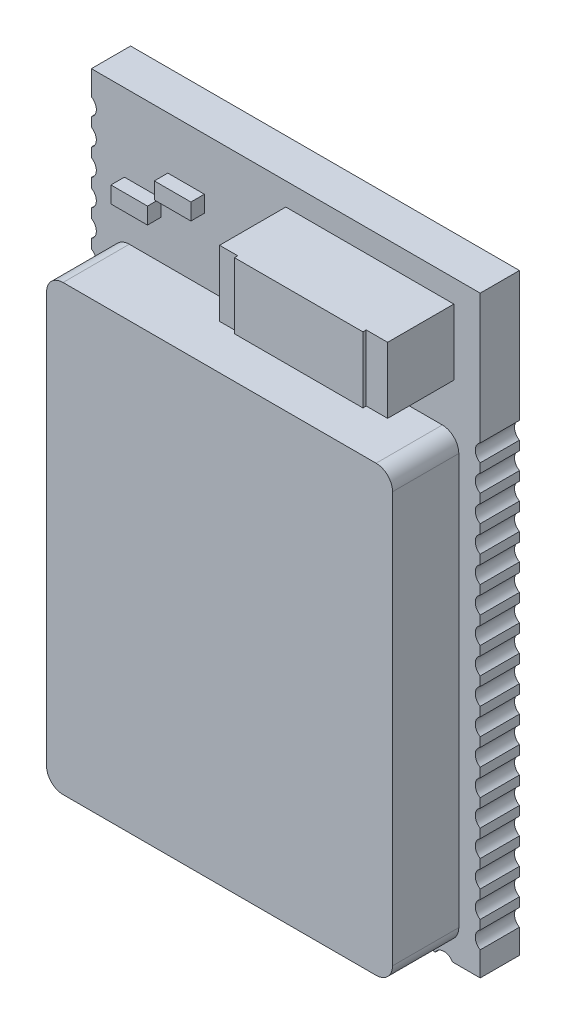
SolidWorks part; units mm, degrees
ref_plane "Front Plane" through (0, 0, 0) normal (0, 0, 1) x (1, 0, 0)
ref_plane "Top Plane" through (0, 0, 0) normal (0, 1, 0) x (1, 0, 0)
ref_plane "Right Plane" through (0, 0, 0) normal (1, 0, 0) x (0, 0, -1)
sketch "Sketch1" plane through (0, 0, 0) normal (0, 0, 1) x (1, 0, 0)
  line L1 (0, 0) -> (11.8, 0)
  line L2 (0, 0) -> (0, 18)
  line L3 (0, 18) -> (11.8, 18)
  line L4 (11.8, 0) -> (11.8, 18)
  dimension "D1" = 11.8
  dimension "D2" = 18
extrude "Boss-Extrude1" add sketch "Sketch1" along normal blind 1.19
sketch "Sketch2" plane through (0, 0, 0) normal (0, 0, 1) x (1, 0, 0)
  line L1 (0.65, 0.5) -> (11.15, 0.5)
  line L2 (0.65, 0.5) -> (0.65, 13.96)
  line L3 (0.65, 13.96) -> (11.15, 13.96)
  line L4 (11.15, 0.5) -> (11.15, 13.96)
extrude "Boss-Extrude2" add sketch "Sketch2" along normal blind 3.2
fillet "Fillet11" radius 0.5 1 edges at (0.65, 13.96, 2.195) type face fillet first side face at (0.65, 7.23, 2.195) second side face at (5.9, 13.96, 2.195)
fillet "Fillet12" radius 0.5 1 edges at (0.65, 0.5, 2.195) type face fillet first side face at (0.65, 6.98, 2.195) second side face at (5.9, 0.5, 2.195)
fillet "Fillet13" radius 0.5 1 edges at (11.15, 0.5, 2.195) type face fillet first side face at (6.15, 0.5, 2.195) second side face at (11.15, 7.23, 2.195)
fillet "Fillet14" radius 0.5 1 edges at (11.15, 13.96, 2.195) type face fillet first side face at (11.15, 7.48, 2.195) second side face at (6.15, 13.96, 2.195)
sketch "Sketch9" plane through (0, 0, 0) normal (0, 0, 1) x (1, 0, 0)
  circle A0 centre (1.1, -0.15) radius 0.3
  circle A1 centre (1.9, -0.15) radius 0.3
  circle A2 centre (2.7, -0.15) radius 0.3
  circle A3 centre (3.5, -0.15) radius 0.3
  circle A4 centre (4.3, -0.15) radius 0.3
  circle A5 centre (5.1, -0.15) radius 0.3
  circle A6 centre (5.9, -0.15) radius 0.3
  circle A7 centre (6.7, -0.15) radius 0.3
  circle A8 centre (7.5, -0.15) radius 0.3
  circle A9 centre (8.3, -0.15) radius 0.3
  circle A10 centre (9.1, -0.15) radius 0.3
  circle A11 centre (9.9, -0.15) radius 0.3
  circle A12 centre (10.7, -0.15) radius 0.3
  dimension "D1" = 13
extrude "Cut-Extrude5" cut sketch "Sketch9" along direction (0, 0, -1) on the side of the normal blind 3.2
sketch "Sketch14" plane through (0, 0, 0) normal (0, 0, 1) x (1, 0, 0)
  line L1 (5.9, 15.3127) -> (11, 15.3127)
  line L2 (5.9, 15.3127) -> (5.9, 17.3127)
  line L3 (5.9, 17.3127) -> (11, 17.3127)
  line L4 (11, 15.3127) -> (11, 17.3127)
extrude "Boss-Extrude3" add sketch "Sketch14" along normal blind 3.2
sketch "Sketch15" plane through (0, 0, 0) normal (0, 0, 1) x (1, 0, 0)
  line L0 (5.9, 15.3127) -> (11, 15.3127) construction
  line L1 (6.451, 15.3127) -> (10.351, 15.3127)
  line L2 (6.451, 15.3127) -> (6.451, 17.3127)
  line L3 (6.451, 17.3127) -> (10.351, 17.3127)
  line L4 (10.351, 15.3127) -> (10.351, 17.3127)
  line L5 (11, 17.3127) -> (5.9, 17.3127) construction
  dimension "D1" = 3.9
extrude "Boss-Extrude4" add sketch "Sketch15" along normal blind 3.3
sketch "Sketch16" plane through (0, 0, 0) normal (0, 0, 1) x (1, 0, 0)
  circle A0 centre (-0.15, 1) radius 0.3
  circle A1 centre (-0.15, 1.8) radius 0.3
  circle A2 centre (-0.15, 2.6) radius 0.3
  circle A3 centre (-0.15, 3.4) radius 0.3
  circle A4 centre (-0.15, 4.2) radius 0.3
  circle A5 centre (-0.15, 5) radius 0.3
  circle A6 centre (-0.15, 5.8) radius 0.3
  circle A7 centre (-0.15, 6.6) radius 0.3
  circle A8 centre (-0.15, 7.4) radius 0.3
  circle A9 centre (-0.15, 8.2) radius 0.3
  circle A10 centre (-0.15, 9) radius 0.3
  circle A11 centre (-0.15, 9.8) radius 0.3
  circle A12 centre (-0.15, 10.6) radius 0.3
  circle A13 centre (-0.15, 11.4) radius 0.3
  circle A14 centre (-0.15, 12.2) radius 0.3
  circle A15 centre (-0.15, 13) radius 0.3
  circle A16 centre (-0.15, 13.8) radius 0.3
  circle A17 centre (-0.15, 14.6) radius 0.3
  circle A18 centre (-0.15, 15.4) radius 0.3
  circle A19 centre (-0.15, 16.2) radius 0.3
  circle A20 centre (-0.15, 17) radius 0.3
  dimension "D1" = 21
extrude "Cut-Extrude6" cut sketch "Sketch16" along normal through all both and the other way through all
sketch "Sketch17" plane through (0, 0, 0) normal (0, 0, 1) x (1, 0, 0)
  circle A0 centre (11.95, 1) radius 0.3
  circle A1 centre (11.95, 1.8) radius 0.3
  circle A2 centre (11.95, 2.6) radius 0.3
  circle A3 centre (11.95, 3.4) radius 0.3
  circle A4 centre (11.95, 4.2) radius 0.3
  circle A5 centre (11.95, 5) radius 0.3
  circle A6 centre (11.95, 5.8) radius 0.3
  circle A7 centre (11.95, 6.6) radius 0.3
  circle A8 centre (11.95, 7.4) radius 0.3
  circle A9 centre (11.95, 8.2) radius 0.3
  circle A10 centre (11.95, 9) radius 0.3
  circle A11 centre (11.95, 9.8) radius 0.3
  circle A12 centre (11.95, 10.6) radius 0.3
  circle A13 centre (11.95, 11.4) radius 0.3
  circle A14 centre (11.95, 12.2) radius 0.3
  circle A15 centre (11.95, 13) radius 0.3
  circle A16 centre (11.95, 13.8) radius 0.3
  dimension "D1" = 17
extrude "Cut-Extrude9" cut sketch "Sketch17" against normal blind 3.2 and the other way through all
sketch "Sketch19" plane through (0, 0, 0) normal (0, 0, 1) x (1, 0, 0)
  line L1 (2.32, 15.9147) -> (3.43, 15.9147)
  line L2 (2.32, 15.9147) -> (2.32, 16.4147)
  line L3 (2.32, 16.4147) -> (3.43, 16.4147)
  line L4 (3.43, 15.9147) -> (3.43, 16.4147)
  dimension "D1" = 1.11
  dimension "D2" = 0.5
extrude "Boss-Extrude6" add sketch "Sketch19" along normal blind 1.6
sketch "Sketch20" plane through (0, 0, 0) normal (0, 0, 1) x (1, 0, 0)
  line L1 (2.1127, 15.6494) -> (1.0027, 15.6494)
  line L2 (2.1127, 15.6494) -> (2.1127, 15.1494)
  line L3 (2.1127, 15.1494) -> (1.0027, 15.1494)
  line L4 (1.0027, 15.6494) -> (1.0027, 15.1494)
  dimension "D1" = 1.11
  dimension "D2" = 0.5
extrude "Boss-Extrude7" add sketch "Sketch20" along normal blind 1.6
